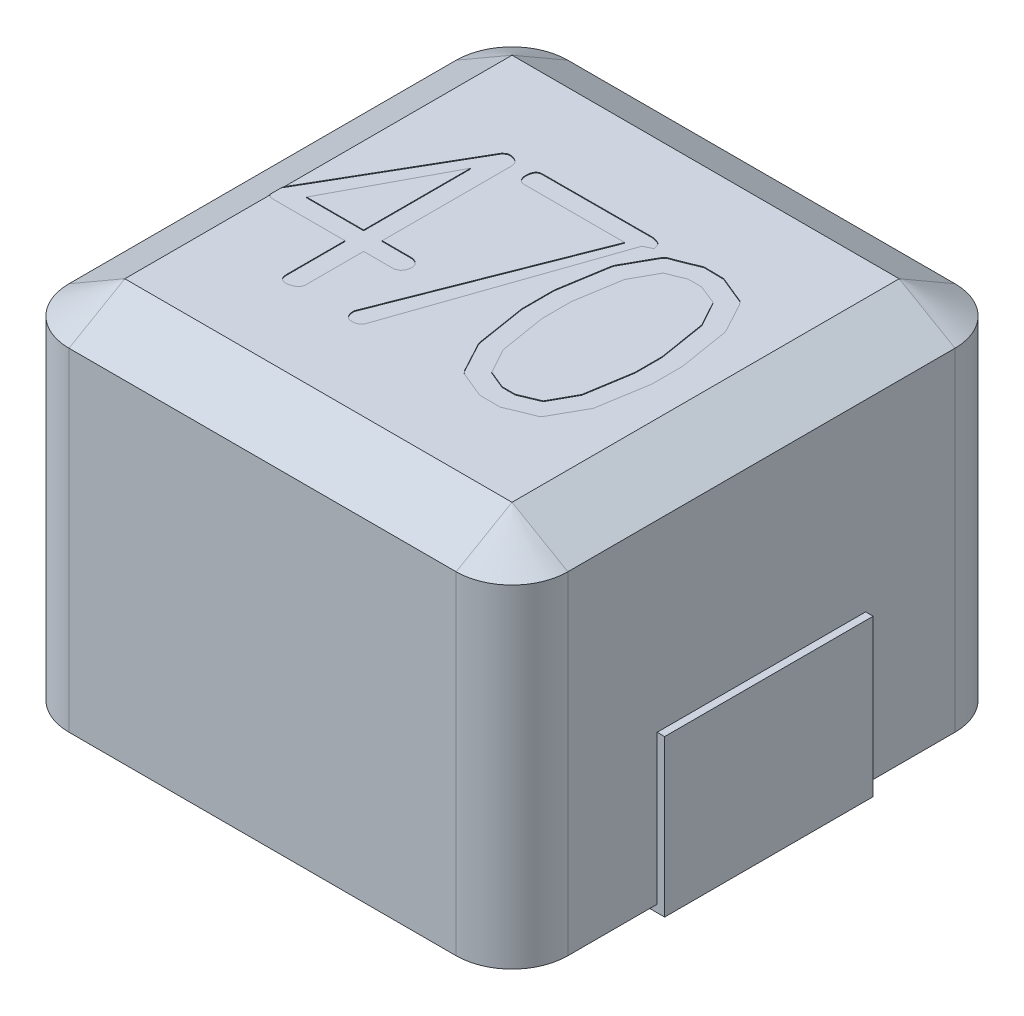
SolidWorks part; units mm, degrees
ref_plane "Front Plane" through (0, 0, 0) normal (0, 0, 1) x (1, 0, 0)
ref_plane "Top Plane" through (0, 0, 0) normal (0, 1, 0) x (1, 0, 0)
ref_plane "Right Plane" through (0, 0, 0) normal (1, 0, 0) x (0, 0, -1)
sketch "Sketch1" plane through (0, 0, 0) normal (0, 1, 0) x (1, 0, 0)
  line L0 (0, 6.4257) -> (0, -7.6623) construction
  line L1 (-1.025, 3.35) -> (1.025, 3.35) construction
  line L2 (-3.35, 1.525) -> (-3.35, -1.525) construction
  line L3 (-1.025, -3.35) -> (1.025, -3.35) construction
  line L4 (3.35, 1.525) -> (3.35, -1.525) construction
  line L5 (-1.675, 1.675) -> (1.675, -1.675) construction
  line L6 (-1.675, -1.675) -> (1.675, 1.675) construction
  line L7 (-1.175, 3.2) -> (-1.175, 1.825) construction
  line L8 (-1.325, 1.675) -> (-3.2, 1.675) construction
  line L9 (0, 0) -> (-4.3179, 0) construction
  line L10 (1.325, 1.675) -> (3.2, 1.675) construction
  line L11 (1.175, 3.2) -> (1.175, 1.825) construction
  line L12 (-1.325, -1.675) -> (-3.2, -1.675) construction
  line L13 (1.325, -1.675) -> (3.2, -1.675) construction
  line L14 (1.175, -3.2) -> (1.175, -1.825) construction
  line L15 (-1.175, -3.2) -> (-1.175, -1.825) construction
  line L16 (-3.35, 3.35) -> (-1.175, 3.35) construction
  line L17 (-3.35, 3.35) -> (-1.675, 1.675) construction
  line L18 (-3.35, 3.35) -> (-3.35, 1.675) construction
  line L19 (1.175, 3.35) -> (3.35, 3.35) construction
  line L20 (1.675, 1.675) -> (3.35, 3.35) construction
  line L21 (3.35, 3.35) -> (3.35, 1.675) construction
  line L22 (3.35, -1.675) -> (3.35, -3.35) construction
  line L23 (1.675, -1.675) -> (3.35, -3.35) construction
  line L24 (1.175, -3.35) -> (3.35, -3.35) construction
  line L25 (-3.35, -3.35) -> (-1.175, -3.35) construction
  line L26 (-3.35, -3.35) -> (-1.675, -1.675) construction
  line L27 (-3.35, -1.675) -> (-3.35, -3.35) construction
  line L29 (2.6, -3.35) -> (-2.6, -3.35)
  line L30 (3.35, -2.6) -> (3.35, 2.6)
  line L31 (2.6, 3.35) -> (-2.6, 3.35)
  line L32 (-3.35, -2.6) -> (-3.35, 2.6)
  line L33 (3.35, -3.35) -> (-3.35, 3.35) construction
  line L34 (3.35, 3.35) -> (-3.35, -3.35) construction
  arc A0 (3.35, -1.525) -> (3.2, -1.675) centre (3.2, -1.525) cw construction
  arc A1 (1.325, -1.675) -> (1.175, -1.825) centre (1.325, -1.825) ccw construction
  arc A2 (1.175, -3.2) -> (1.025, -3.35) centre (1.025, -3.2) cw construction
  arc A3 (-1.025, -3.35) -> (-1.175, -3.2) centre (-1.025, -3.2) cw construction
  arc A4 (-1.175, -1.825) -> (-1.325, -1.675) centre (-1.325, -1.825) ccw construction
  arc A5 (-3.2, -1.675) -> (-3.35, -1.525) centre (-3.2, -1.525) cw construction
  arc A6 (-3.35, 1.525) -> (-3.2, 1.675) centre (-3.2, 1.525) cw construction
  arc A7 (3.35, 1.525) -> (3.2, 1.675) centre (3.2, 1.525) ccw construction
  arc A8 (1.325, 1.675) -> (1.175, 1.825) centre (1.325, 1.825) cw construction
  arc A9 (1.175, 3.2) -> (1.025, 3.35) centre (1.025, 3.2) ccw construction
  arc A10 (-1.325, 1.675) -> (-1.175, 1.825) centre (-1.325, 1.825) ccw construction
  arc A11 (-1.175, 3.2) -> (-1.025, 3.35) centre (-1.025, 3.2) cw construction
  arc A12 (3.35, -2.6) -> (2.6, -3.35) centre (2.6, -2.6) cw
  arc A13 (-2.6, -3.35) -> (-3.35, -2.6) centre (-2.6, -2.6) cw
  arc A14 (3.35, 2.6) -> (2.6, 3.35) centre (2.6, 2.6) ccw
  arc A15 (-3.35, 2.6) -> (-2.6, 3.35) centre (-2.6, 2.6) cw
  point P0 (0, 0)
  point P38 (1.175, -1.675)
  point P47 (-1.175, -1.675)
  point P59 (1.175, 1.675)
  point P65 (-1.175, 1.675)
  point P74 (-6.7231, 1.495)
  dimension "D5" = 0.15
  dimension "D6" = 0.75
  dimension "D1" = 6.7
  dimension "D2" = 1.175
  dimension "D3" = 1.675
  dimension "D4" = 6.7
extrude "Boss-Extrude1" add sketch "Sketch1" along normal blind 4.9
sketch "Sketch4" plane through (0, 0, 0) normal (0, -1, 0) x (1, 0, 0)
  line L3 (0, 3.35) -> (0, -3.35) construction
  line L24 (-2.6, 3.35) -> (2.6, 3.35) construction
  line L25 (2.6, -3.35) -> (-2.6, -3.35) construction
  line L26 (-3.45, 1.4) -> (-2, 1.4)
  line L28 (-2, 1.4) -> (-2, -1.4)
  line L29 (-2, -1.4) -> (-3.45, -1.4)
  line L30 (-3.45, -1.4) -> (-3.45, 1.4)
  line L31 (0, 0) -> (-5.1227, 0) construction
  line L32 (2, -1.4) -> (3.45, -1.4)
  line L33 (2, 1.4) -> (2, -1.4)
  line L34 (3.45, 1.4) -> (2, 1.4)
  line L35 (3.45, -1.4) -> (3.45, 1.4)
  line L36 (-3.35, -2.6) -> (-3.35, 2.6) construction
  point P8 (-3.4085, -1.4)
  point P18 (0, 0)
  point P19 (0, 0)
  dimension "D1" = 2.8
  dimension "D2" = 4
  dimension "D3" = 0.1
extrude "Boss-Extrude3" add sketch "Sketch4" against normal blind 2 and the other way blind 0.1
chamfer "Chamfer1" distance 0.75 angle 30 8 edges at (0, 4.9, -3.35) (-3.1303, 4.9, -3.1303) (3.1303, 4.9, -3.1303) (-3.35, 4.9, 0) (3.35, 4.9, 0) (-3.1303, 4.9, 3.1303) (3.1303, 4.9, 3.1303) (0, 4.9, 3.35) first distance on face at (0, 4.9, 0)
sketch "Sketch5" plane through (0, 4.9, 0) normal (0, 1, 0) x (1, 0, 0)
  line L0 (-2.6, -1.5) -> (2.6, -1.5) construction
  line L1 (0, 3.35) -> (0, -3.35) construction
  line L2 (-2.6, 3.35) -> (2.6, 3.35) construction
  line L3 (2.6, -3.35) -> (-2.6, -3.35) construction
  line L4 (-2.6, 2.6) -> (-2.6, -2.6) construction
  text T0 "470" font "SWSimp" height 3
  point P8 (0, 0)
  point P9 (0, 0)
  point P12 (-2.6, -2)
  dimension "D1" = 1.5
extrude "Cut-Extrude1" cut sketch "Sketch5" against normal blind 0.01
